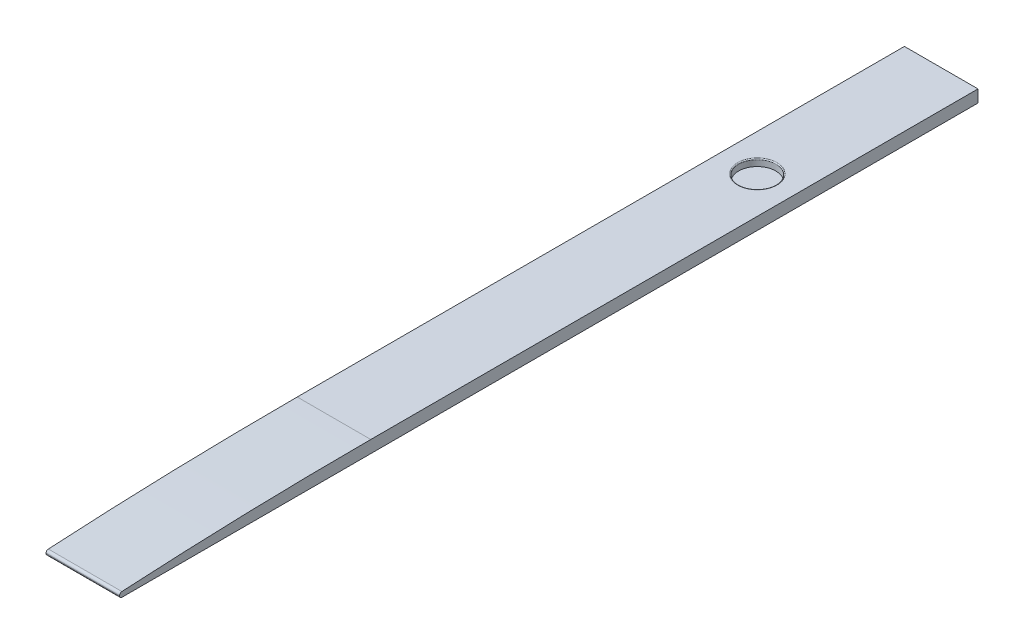
SolidWorks part; units mm, degrees
ref_plane "前视基准面" through (0, 0, 0) normal (0, 0, 1) x (1, 0, 0)
ref_plane "上视基准面" through (0, 0, 0) normal (0, 1, 0) x (1, 0, 0)
ref_plane "右视基准面" through (0, 0, 0) normal (1, 0, 0) x (0, 0, -1)
other "Configuration Table"
sketch "草图1" plane through (0, 0, 0) normal (1, 0, 0) x (0, 0, -1)
  line L0 (0, 0) -> (-350, 0)
  line L5 (0, 5) -> (0, 0)
  line L6 (-300, 5) -> (0, 5)
  line L7 (-350, 0) -> (-350, 2)
  line L8 (-350, 2) -> (-300, 5)
  dimension "D1" = 350
  dimension "D2" = 5
  dimension "D3" = 2
  dimension "D7" = 50
extrude "凸台-拉伸1" add sketch "草图1" along normal blind 30
fillet "圆角1" radius 1750 1 edges at (15, 5, 300)
sketch "草图4" plane through (0, 5, 0) normal (0, 1, 0) x (1, 0, 0)
  line L0 (15, 0) -> (15, -75) construction
  line L1 (30, 0) -> (0, 0) construction
  line L2 (15, 0) -> (15, -40) construction
  circle A0 centre (15, -75) radius 7.6
  dimension "D2" = 15.2
  dimension "D1" = 75
extrude "切除-拉伸3" cut sketch "草图4" against normal blind 2.8
fillet "圆角4" radius 0.4 1 edges at (15, 5, 82.6)
sketch "草图5" plane through (0, 0, 0) normal (0, 0, -1) x (-1, 0, 0)
  line L0 (0, 0) -> (0, 5) construction
  line L1 (-25, 3.5) -> (-5, 3.5)
  line L2 (-25, 3.5) -> (-25, 1.5)
  line L3 (-25, 1.5) -> (-5, 1.5)
  line L4 (-5, 3.5) -> (-5, 1.5)
  line L5 (-30, 0) -> (-30, 5) construction
  line L6 (-30, 5) -> (0, 5) construction
  line L7 (-30, 0) -> (0, 0) construction
  dimension "D1" = 5
  dimension "D2" = 5
  dimension "D3" = 1.5
  dimension "D4" = 1.5
extrude "切除-拉伸4" cut sketch "草图5" against normal blind 25
fillet "圆角5" radius 1 2 edges at (15, 0, 350) (15, 2, 350)
